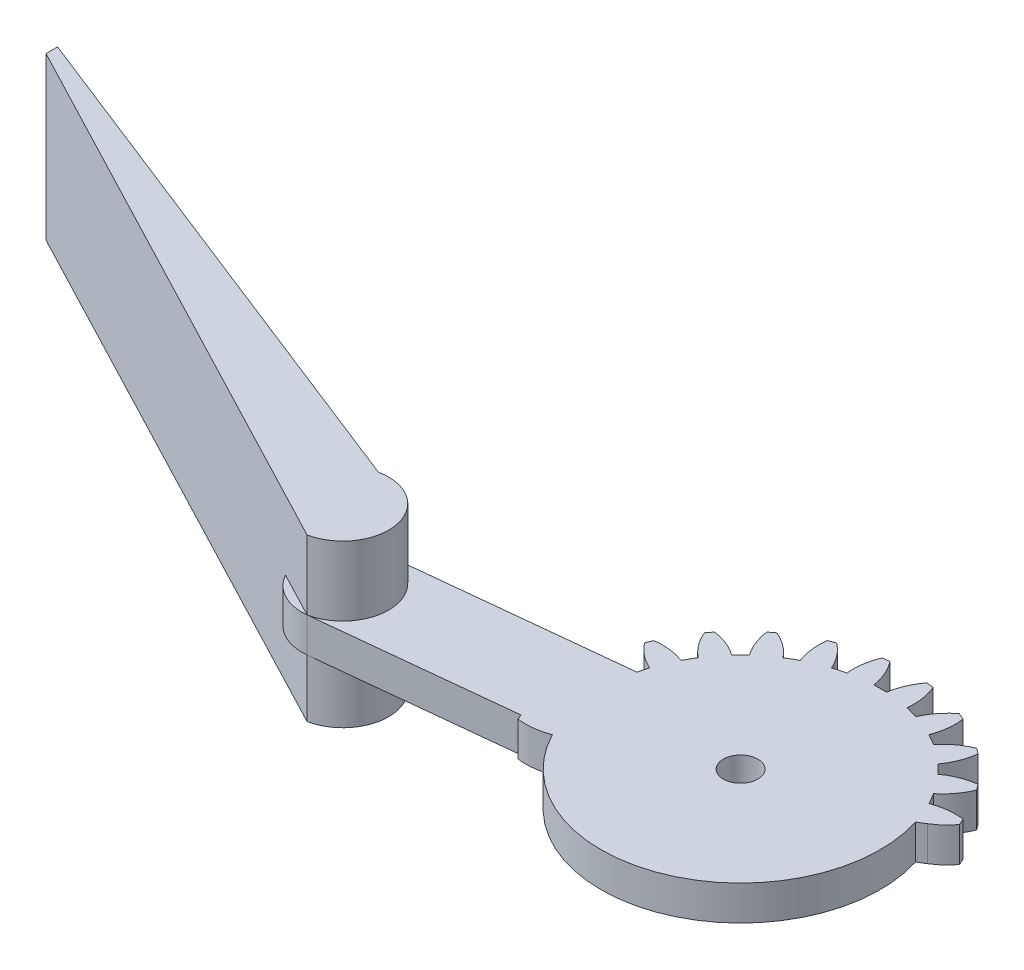
SolidWorks part; units mm, degrees
ref_plane "Front Plane" through (0, 0, 0) normal (0, 0, 1) x (1, 0, 0)
ref_plane "Top Plane" through (0, 0, 0) normal (0, 1, 0) x (1, 0, 0)
ref_plane "Right Plane" through (0, 0, 0) normal (1, 0, 0) x (0, 0, -1)
sketch "Sketch1" plane through (0, 0, 0) normal (0, 1, 0) x (1, 0, 0)
  line L0 (20.6437, 4) -> (2.0816, 4)
  line L1 (2.0816, -4) -> (20.6437, -4)
  arc A0 (2.0816, 4) -> (3.5217, 5.3071) centre (-0.7683, 8.5867) ccw
  arc A1 (3.5217, 5.3071) -> (3.2829, 5.8838) centre (-10.1063, 0) ccw
  arc A2 (3.2829, 5.8838) -> (0.6271, 5.5703) centre (2.5684, 0.5313) ccw
  arc A3 (0.6271, 5.5703) -> (0.0844, 6.5103) centre (-10.1063, 0) ccw
  arc A4 (0.0844, 6.5103) -> (1.6838, 8.6535) centre (-3.3089, 10.711) ccw
  arc A5 (1.6838, 8.6535) -> (1.3038, 9.1487) centre (-10.1063, 0) ccw
  arc A6 (1.3038, 9.1487) -> (-1.1803, 8.1585) centre (1.999, 3.7936) ccw
  arc A7 (-1.1803, 8.1585) -> (-1.9479, 8.926) centre (-10.1063, 0) ccw
  arc A8 (-1.9479, 8.926) -> (-0.9576, 11.4102) centre (-6.3127, 12.1053) ccw
  arc A9 (-0.9576, 11.4102) -> (-1.4528, 11.7901) centre (-10.1063, 0) ccw
  arc A10 (-1.4528, 11.7901) -> (-3.596, 10.1907) centre (0.6046, 6.7975) ccw
  arc A11 (-3.596, 10.1907) -> (-4.5361, 10.7334) centre (-10.1063, 0) ccw
  arc A12 (-4.5361, 10.7334) -> (-4.2225, 13.3892) centre (-9.5751, 12.6747) ccw
  arc A13 (-4.2225, 13.3892) -> (-4.7992, 13.6281) centre (-10.1063, 0) ccw
  arc A14 (-4.7992, 13.6281) -> (-6.4554, 11.5285) centre (-1.5196, 9.3381) ccw
  arc A15 (-6.4554, 11.5285) -> (-7.5039, 11.8094) centre (-10.1063, 0) ccw
  arc A16 (-7.5039, 11.8094) -> (-7.8884, 14.4558) centre (-12.8736, 12.3803) ccw
  arc A17 (-7.8884, 14.4558) -> (-8.5072, 14.5373) centre (-10.1063, 0) ccw
  arc A18 (-8.5072, 14.5373) -> (-9.5636, 12.0806) centre (-4.2291, 11.2423) ccw
  arc A19 (-9.5636, 12.0806) -> (-10.6491, 12.0806) centre (-10.1063, 0) ccw
  arc A20 (-10.6491, 12.0806) -> (-11.7054, 14.5373) centre (-15.9836, 11.2423) ccw
  arc A21 (-11.7054, 14.5373) -> (-12.3243, 14.4558) centre (-10.1063, 0) ccw
  arc A22 (-12.3243, 14.4558) -> (-12.7088, 11.8094) centre (-7.3391, 12.3803) ccw
  arc A23 (-12.7088, 11.8094) -> (-13.7573, 11.5285) centre (-10.1063, 0) ccw
  arc A24 (-13.7573, 11.5285) -> (-15.4135, 13.6281) centre (-18.6931, 9.3381) ccw
  arc A25 (-15.4135, 13.6281) -> (-15.9901, 13.3892) centre (-10.1063, 0) ccw
  arc A26 (-15.9901, 13.3892) -> (-15.6766, 10.7334) centre (-10.6376, 12.6747) ccw
  arc A27 (-15.6766, 10.7334) -> (-16.6166, 10.1907) centre (-10.1063, 0) ccw
  arc A28 (-16.6166, 10.1907) -> (-18.7599, 11.7901) centre (-20.8173, 6.7975) ccw
  arc A29 (-18.7599, 11.7901) -> (-19.255, 11.4102) centre (-10.1063, 0) ccw
  arc A30 (-19.255, 11.4102) -> (-18.2648, 8.926) centre (-13.9, 12.1053) ccw
  arc A31 (-18.2648, 8.926) -> (-19.0324, 8.1585) centre (-10.1063, 0) ccw
  arc A32 (-19.0324, 8.1585) -> (-21.5165, 9.1487) centre (-22.2117, 3.7936) ccw
  arc A33 (-21.5165, 9.1487) -> (-21.8965, 8.6535) centre (-10.1063, 0) ccw
  arc A34 (-21.8965, 8.6535) -> (-20.2971, 6.5103) centre (-16.9038, 10.711) ccw
  arc A35 (-20.2971, 6.5103) -> (-20.8398, 5.5703) centre (-10.1063, 0) ccw
  arc A36 (-20.8398, 5.5703) -> (-23.4956, 5.8838) centre (-22.7811, 0.5313) ccw
  arc A37 (-23.4956, 5.8838) -> (-23.7344, 5.3071) centre (-10.1063, 0) ccw
  arc A38 (-23.7344, 5.3071) -> (-21.6348, 3.6509) centre (-19.4444, 8.5867) ccw
  arc A39 (-21.6348, 3.6509) -> (-21.9157, 2.6025) centre (-10.1063, 0) ccw
  arc A40 (-21.9157, 2.6025) -> (-24.5622, 2.2179) centre (-22.4867, -2.7673) ccw
  arc A41 (-24.5622, 2.2179) -> (-24.6437, 1.5991) centre (-10.1063, 0) ccw
  arc A42 (-24.6437, 1.5991) -> (-22.1869, 0.5427) centre (-21.3486, 5.8773) ccw
  arc A43 (-22.1869, 0.5427) -> (-22.1869, -0.5427) centre (-10.1063, 0) ccw
  arc A44 (-22.1869, -0.5427) -> (-24.6437, -1.5991) centre (-21.3486, -5.8773) ccw
  arc A45 (-24.6437, -1.5991) -> (-24.5622, -2.2179) centre (-10.1063, 0) ccw
  arc A46 (-24.5622, -2.2179) -> (-21.9157, -2.6025) centre (-22.4867, 2.7673) ccw
  arc A47 (-21.9157, -2.6025) -> (-21.6348, -3.6509) centre (-10.1063, 0) ccw
  arc A48 (-21.6348, -3.6509) -> (-23.7344, -5.3071) centre (-19.4444, -8.5867) ccw
  arc A49 (-23.7344, -5.3071) -> (-23.4956, -5.8838) centre (-10.1063, 0) ccw
  arc A50 (-23.4956, -5.8838) -> (-20.8398, -5.5703) centre (-22.7811, -0.5313) ccw
  arc A51 (-20.8398, -5.5703) -> (-20.2971, -6.5103) centre (-10.1063, 0) ccw
  arc A52 (-20.2971, -6.5103) -> (-21.8965, -8.6535) centre (-16.9038, -10.711) ccw
  arc A53 (-21.8965, -8.6535) -> (-21.5165, -9.1487) centre (-10.1063, 0) ccw
  arc A54 (-21.5165, -9.1487) -> (-19.0324, -8.1585) centre (-22.2117, -3.7936) ccw
  arc A55 (-19.0324, -8.1585) -> (-18.2648, -8.926) centre (-10.1063, 0) ccw
  arc A56 (-18.2648, -8.926) -> (-19.255, -11.4102) centre (-13.9, -12.1053) ccw
  arc A57 (-19.255, -11.4102) -> (-18.7599, -11.7901) centre (-10.1063, 0) ccw
  arc A58 (-18.7599, -11.7901) -> (-16.6166, -10.1907) centre (-20.8173, -6.7975) ccw
  arc A59 (-16.6166, -10.1907) -> (-15.6766, -10.7334) centre (-10.1063, 0) ccw
  arc A60 (-15.6766, -10.7334) -> (-15.9901, -13.3892) centre (-10.6376, -12.6747) ccw
  arc A61 (-15.9901, -13.3892) -> (-15.4135, -13.6281) centre (-10.1063, 0) ccw
  arc A62 (-15.4135, -13.6281) -> (-13.7573, -11.5285) centre (-18.6931, -9.3381) ccw
  arc A63 (-13.7573, -11.5285) -> (-12.7088, -11.8094) centre (-10.1063, 0) ccw
  arc A64 (-12.7088, -11.8094) -> (-12.3243, -14.4558) centre (-7.3391, -12.3803) ccw
  arc A65 (-12.3243, -14.4558) -> (-11.7054, -14.5373) centre (-10.1063, 0) ccw
  arc A66 (-11.7054, -14.5373) -> (-10.6491, -12.0806) centre (-15.9836, -11.2423) ccw
  arc A67 (-10.6491, -12.0806) -> (-9.5636, -12.0806) centre (-10.1063, 0) ccw
  arc A68 (-9.5636, -12.0806) -> (-8.5072, -14.5373) centre (-4.2291, -11.2423) ccw
  arc A69 (-8.5072, -14.5373) -> (-7.8884, -14.4558) centre (-10.1063, 0) ccw
  arc A70 (-7.8884, -14.4558) -> (-7.5039, -11.8094) centre (-12.8736, -12.3803) ccw
  arc A71 (-7.5039, -11.8094) -> (-6.4554, -11.5285) centre (-10.1063, 0) ccw
  arc A72 (-6.4554, -11.5285) -> (-4.7992, -13.6281) centre (-1.5196, -9.3381) ccw
  arc A73 (-4.7992, -13.6281) -> (-4.2225, -13.3892) centre (-10.1063, 0) ccw
  arc A74 (-4.2225, -13.3892) -> (-4.5361, -10.7334) centre (-9.5751, -12.6747) ccw
  arc A75 (-4.5361, -10.7334) -> (-3.596, -10.1907) centre (-10.1063, 0) ccw
  arc A76 (-3.596, -10.1907) -> (-1.4528, -11.7901) centre (0.6046, -6.7975) ccw
  arc A77 (-1.4528, -11.7901) -> (-0.9576, -11.4102) centre (-10.1063, 0) ccw
  arc A78 (-0.9576, -11.4102) -> (-1.9479, -8.926) centre (-6.3127, -12.1053) ccw
  arc A79 (-1.9479, -8.926) -> (-1.1803, -8.1585) centre (-10.1063, 0) ccw
  arc A80 (-1.1803, -8.1585) -> (1.3038, -9.1487) centre (1.999, -3.7936) ccw
  arc A81 (1.3038, -9.1487) -> (1.6838, -8.6535) centre (-10.1063, 0) ccw
  arc A82 (1.6838, -8.6535) -> (0.0844, -6.5103) centre (-3.3089, -10.711) ccw
  arc A83 (0.0844, -6.5103) -> (0.6271, -5.5703) centre (-10.1063, 0) ccw
  arc A84 (0.6271, -5.5703) -> (3.2829, -5.8838) centre (2.5684, -0.5313) ccw
  arc A85 (3.2829, -5.8838) -> (3.5217, -5.3071) centre (-10.1063, 0) ccw
  arc A86 (3.5217, -5.3071) -> (2.0816, -4) centre (-0.7683, -8.5867) ccw
  arc A87 (20.6437, -4) -> (20.6437, 4) centre (20.6437, 0) ccw
  circle A88 centre (-10.1063, 0) radius 1.5
  circle A89 centre (20.6437, 0) radius 1.5
  dimension "D1" = 3
  dimension "D2" = 3
extrude "Boss-Extrude1" add sketch "Sketch1" along normal blind 3
sketch "Sketch3" plane through (0, 3, 0) normal (0, 1, 0) x (1, 0, 0)
  line L0 (-10.1063, 0) -> (-40.8563, 0) construction
  line L1 (-10.1063, 0) -> (-40.8563, -3.232)
  line L2 (-10.5245, 3.9781) -> (-41.2745, 0.7461)
  line L3 (-9.6882, -3.9781) -> (-40.4382, -7.21)
  circle A0 centre (-10.1063, 0) radius 1.5
  circle A1 centre (20.6437, 0) radius 1.5 construction
  circle A2 centre (20.6437, 0) radius 1.5
  circle A3 centre (-40.8563, -3.232) radius 1.5
  circle A4 centre (-40.8563, -3.232) radius 4
  circle A5 centre (-10.1063, 0) radius 4
  dimension "D2" = 3
  dimension "D5" = 3
  dimension "D6" = 8
  dimension "D7" = 8
  dimension "D1" = 30.75
  dimension "D3" = 30.75
  dimension "D4" = 6
extrude "Boss-Extrude2" add sketch "Sketch3" against normal blind 3 contours L0 A5 L2 | A5 L0 L2 A4 L1 | A4 A3 | A5 L1 A4 L3 | L0 A0 L1 A5 | A0 L0 A5 L1 region at (-13.0404, 3, 0.1538) region at (-12.8563, 3, -0.1131) region at (-28.6602, 3, 0.9475) region at (-23.811, 3, -1.3402) region at (-25.2642, 3, 3.6817) region at (-37.4885, 3, 1.2915)
sketch "Sketch4" plane through (0, 3, 0) normal (0, 1, 0) x (1, 0, 0)
  line L0 (20.6437, 4) -> (2.0816, 4) construction
  line L1 (2.0816, -4) -> (20.6437, -4) construction
  line L2 (20.6437, 4) -> (2.0816, 4)
  line L3 (2.0816, -4) -> (20.6437, -4)
  line L4 (2.0816, 4) -> (1.4381, 3.6001)
  line L5 (-23.2182, -5.4001) -> (-21.0377, -5.171)
  line L8 (-21.874, 2.7852) -> (-41.2745, 0.7461)
  line L9 (-40.4382, -7.21) -> (-23.6785, -5.4485)
  line L10 (2.0816, -4) -> (20.6437, -4)
  line L11 (20.6437, 4) -> (2.0816, 4)
  line L12 (-21.874, 2.7852) -> (-41.2745, 0.7461)
  line L13 (-40.4382, -7.21) -> (-23.6785, -5.4485)
  line L14 (2.0816, -4) -> (20.6437, -4)
  line L15 (20.6437, 4) -> (2.0816, 4)
  circle A0 centre (-10.1063, 0) radius 12.0927
  arc A1 (3.2829, 5.8838) -> (0.6271, 5.5703) centre (2.5684, 0.5313) ccw construction
  arc A2 (3.5217, 5.3071) -> (3.2829, 5.8838) centre (-10.1063, 0) ccw construction
  arc A3 (2.0816, 4) -> (3.5217, 5.3071) centre (-0.7683, 8.5867) ccw construction
  arc A4 (20.6437, -4) -> (20.6437, 4) centre (20.6437, 0) ccw construction
  arc A5 (3.5217, -5.3071) -> (2.0816, -4) centre (-0.7683, -8.5867) ccw construction
  arc A6 (3.2829, -5.8838) -> (3.5217, -5.3071) centre (-10.1063, 0) ccw construction
  arc A7 (0.6271, -5.5703) -> (3.2829, -5.8838) centre (2.5684, -0.5313) ccw construction
  arc A8 (3.2829, 5.8838) -> (0.6271, 5.5703) centre (2.5684, 0.5313) ccw
  arc A9 (3.5217, 5.3071) -> (3.2829, 5.8838) centre (-10.1063, 0) ccw
  arc A10 (2.0816, 4) -> (3.5217, 5.3071) centre (-0.7683, 8.5867) ccw
  arc A11 (20.6437, -4) -> (20.6437, 4) centre (20.6437, 0) ccw
  arc A12 (3.5217, -5.3071) -> (2.0816, -4) centre (-0.7683, -8.5867) ccw
  arc A13 (3.2829, -5.8838) -> (3.5217, -5.3071) centre (-10.1063, 0) ccw
  arc A14 (0.6271, -5.5703) -> (3.2829, -5.8838) centre (2.5684, -0.5313) ccw
  arc A95 (-23.6785, -5.4485) -> (-23.4956, -5.8838) centre (-10.1063, 0) ccw
  arc A96 (-41.2745, 0.7461) -> (-40.4382, -7.21) centre (-40.8563, -3.232) ccw
  arc A97 (-20.2971, -6.5103) -> (-21.8965, -8.6535) centre (-16.9038, -10.711) ccw
  arc A98 (-21.8965, -8.6535) -> (-21.5165, -9.1487) centre (-10.1063, 0) ccw
  arc A99 (-21.5165, -9.1487) -> (-19.0324, -8.1585) centre (-22.2117, -3.7936) ccw
  arc A100 (-19.0324, -8.1585) -> (-18.2648, -8.926) centre (-10.1063, 0) ccw
  arc A101 (-18.2648, -8.926) -> (-19.255, -11.4102) centre (-13.9, -12.1053) ccw
  arc A102 (-19.255, -11.4102) -> (-18.7599, -11.7901) centre (-10.1063, 0) ccw
  arc A103 (-18.7599, -11.7901) -> (-16.6166, -10.1907) centre (-20.8173, -6.7975) ccw
  arc A104 (-16.6166, -10.1907) -> (-15.6766, -10.7334) centre (-10.1063, 0) ccw
  arc A105 (-15.6766, -10.7334) -> (-15.9901, -13.3892) centre (-10.6376, -12.6747) ccw
  arc A106 (-15.9901, -13.3892) -> (-15.4135, -13.6281) centre (-10.1063, 0) ccw
  arc A107 (-15.4135, -13.6281) -> (-13.7573, -11.5285) centre (-18.6931, -9.3381) ccw
  arc A108 (-13.7573, -11.5285) -> (-12.7088, -11.8094) centre (-10.1063, 0) ccw
  arc A109 (-12.7088, -11.8094) -> (-12.3243, -14.4558) centre (-7.3391, -12.3803) ccw
  arc A110 (-12.3243, -14.4558) -> (-11.7054, -14.5373) centre (-10.1063, 0) ccw
  arc A111 (-11.7054, -14.5373) -> (-10.6491, -12.0806) centre (-15.9836, -11.2423) ccw
  arc A112 (-10.6491, -12.0806) -> (-9.5636, -12.0806) centre (-10.1063, 0) ccw
  arc A113 (-9.5636, -12.0806) -> (-8.5072, -14.5373) centre (-4.2291, -11.2423) ccw
  arc A114 (-8.5072, -14.5373) -> (-7.8884, -14.4558) centre (-10.1063, 0) ccw
  arc A115 (-7.8884, -14.4558) -> (-7.5039, -11.8094) centre (-12.8736, -12.3803) ccw
  arc A116 (-7.5039, -11.8094) -> (-6.4554, -11.5285) centre (-10.1063, 0) ccw
  arc A117 (-6.4554, -11.5285) -> (-4.7992, -13.6281) centre (-1.5196, -9.3381) ccw
  arc A118 (-4.7992, -13.6281) -> (-4.2225, -13.3892) centre (-10.1063, 0) ccw
  arc A119 (-4.2225, -13.3892) -> (-4.5361, -10.7334) centre (-9.5751, -12.6747) ccw
  arc A120 (-4.5361, -10.7334) -> (-3.596, -10.1907) centre (-10.1063, 0) ccw
  arc A121 (-3.596, -10.1907) -> (-1.4528, -11.7901) centre (0.6046, -6.7975) ccw
  arc A122 (-1.4528, -11.7901) -> (-0.9576, -11.4102) centre (-10.1063, 0) ccw
  arc A123 (-0.9576, -11.4102) -> (-1.9479, -8.926) centre (-6.3127, -12.1053) ccw
  arc A124 (-1.9479, -8.926) -> (-1.1803, -8.1585) centre (-10.1063, 0) ccw
  arc A125 (-1.1803, -8.1585) -> (1.3038, -9.1487) centre (1.999, -3.7936) ccw
  arc A126 (1.3038, -9.1487) -> (1.6838, -8.6535) centre (-10.1063, 0) ccw
  arc A127 (1.6838, -8.6535) -> (0.0844, -6.5103) centre (-3.3089, -10.711) ccw
  arc A128 (0.0844, -6.5103) -> (0.6271, -5.5703) centre (-10.1063, 0) ccw
  arc A129 (0.6271, -5.5703) -> (3.2829, -5.8838) centre (2.5684, -0.5313) ccw
  arc A130 (3.2829, -5.8838) -> (3.5217, -5.3071) centre (-10.1063, 0) ccw
  arc A131 (3.5217, -5.3071) -> (2.0816, -4) centre (-0.7683, -8.5867) ccw
  arc A132 (20.6437, -4) -> (20.6437, 4) centre (20.6437, 0) ccw
  arc A133 (2.0816, 4) -> (3.5217, 5.3071) centre (-0.7683, 8.5867) ccw
  arc A134 (3.5217, 5.3071) -> (3.2829, 5.8838) centre (-10.1063, 0) ccw
  arc A135 (3.2829, 5.8838) -> (0.6271, 5.5703) centre (2.5684, 0.5313) ccw
  arc A136 (0.6271, 5.5703) -> (0.0844, 6.5103) centre (-10.1063, 0) ccw
  arc A137 (0.0844, 6.5103) -> (1.6838, 8.6535) centre (-3.3089, 10.711) ccw
  arc A138 (1.6838, 8.6535) -> (1.3038, 9.1487) centre (-10.1063, 0) ccw
  arc A139 (1.3038, 9.1487) -> (-1.1803, 8.1585) centre (1.999, 3.7936) ccw
  arc A140 (-1.1803, 8.1585) -> (-1.9479, 8.926) centre (-10.1063, 0) ccw
  arc A141 (-1.9479, 8.926) -> (-0.9576, 11.4102) centre (-6.3127, 12.1053) ccw
  arc A142 (-0.9576, 11.4102) -> (-1.4528, 11.7901) centre (-10.1063, 0) ccw
  arc A143 (-1.4528, 11.7901) -> (-3.596, 10.1907) centre (0.6046, 6.7975) ccw
  arc A144 (-3.596, 10.1907) -> (-4.5361, 10.7334) centre (-10.1063, 0) ccw
  arc A145 (-4.5361, 10.7334) -> (-4.2225, 13.3892) centre (-9.5751, 12.6747) ccw
  arc A146 (-4.2225, 13.3892) -> (-4.7992, 13.6281) centre (-10.1063, 0) ccw
  arc A147 (-4.7992, 13.6281) -> (-6.4554, 11.5285) centre (-1.5196, 9.3381) ccw
  arc A148 (-6.4554, 11.5285) -> (-7.5039, 11.8094) centre (-10.1063, 0) ccw
  arc A149 (-7.5039, 11.8094) -> (-7.8884, 14.4558) centre (-12.8736, 12.3803) ccw
  arc A150 (-7.8884, 14.4558) -> (-8.5072, 14.5373) centre (-10.1063, 0) ccw
  arc A151 (-8.5072, 14.5373) -> (-9.5636, 12.0806) centre (-4.2291, 11.2423) ccw
  arc A152 (-9.5636, 12.0806) -> (-10.6491, 12.0806) centre (-10.1063, 0) ccw
  arc A153 (-10.6491, 12.0806) -> (-11.7054, 14.5373) centre (-15.9836, 11.2423) ccw
  arc A154 (-11.7054, 14.5373) -> (-12.3243, 14.4558) centre (-10.1063, 0) ccw
  arc A155 (-12.3243, 14.4558) -> (-12.7088, 11.8094) centre (-7.3391, 12.3803) ccw
  arc A156 (-12.7088, 11.8094) -> (-13.7573, 11.5285) centre (-10.1063, 0) ccw
  arc A157 (-13.7573, 11.5285) -> (-15.4135, 13.6281) centre (-18.6931, 9.3381) ccw
  arc A158 (-15.4135, 13.6281) -> (-15.9901, 13.3892) centre (-10.1063, 0) ccw
  arc A159 (-15.9901, 13.3892) -> (-15.6766, 10.7334) centre (-10.6376, 12.6747) ccw
  arc A160 (-15.6766, 10.7334) -> (-16.6166, 10.1907) centre (-10.1063, 0) ccw
  arc A161 (-16.6166, 10.1907) -> (-18.7599, 11.7901) centre (-20.8173, 6.7975) ccw
  arc A162 (-18.7599, 11.7901) -> (-19.255, 11.4102) centre (-10.1063, 0) ccw
  arc A163 (-19.255, 11.4102) -> (-18.2648, 8.926) centre (-13.9, 12.1053) ccw
  arc A164 (-18.2648, 8.926) -> (-19.0324, 8.1585) centre (-10.1063, 0) ccw
  arc A165 (-19.0324, 8.1585) -> (-21.5165, 9.1487) centre (-22.2117, 3.7936) ccw
  arc A166 (-21.5165, 9.1487) -> (-21.8965, 8.6535) centre (-10.1063, 0) ccw
  arc A167 (-21.8965, 8.6535) -> (-20.2971, 6.5103) centre (-16.9038, 10.711) ccw
  arc A168 (-20.2971, 6.5103) -> (-20.8398, 5.5703) centre (-10.1063, 0) ccw
  arc A169 (-20.8398, 5.5703) -> (-23.4956, 5.8838) centre (-22.7811, 0.5313) ccw
  arc A170 (-23.4956, 5.8838) -> (-23.7344, 5.3071) centre (-10.1063, 0) ccw
  arc A171 (-23.7344, 5.3071) -> (-21.6348, 3.6509) centre (-19.4444, 8.5867) ccw
  arc A172 (-21.6348, 3.6509) -> (-21.874, 2.7852) centre (-10.1063, 0) ccw
  arc A173 (-23.6785, -5.4485) -> (-23.4956, -5.8838) centre (-10.1063, 0) ccw
  arc A174 (-23.4956, -5.8838) -> (-20.8398, -5.5703) centre (-22.7811, -0.5313) ccw
  arc A175 (-23.4956, -5.8838) -> (-20.8398, -5.5703) centre (-22.7811, -0.5313) ccw
  arc A176 (-41.2745, 0.7461) -> (-40.4382, -7.21) centre (-40.8563, -3.232) ccw
  arc A177 (-20.2971, -6.5103) -> (-21.8965, -8.6535) centre (-16.9038, -10.711) ccw
  arc A178 (-21.8965, -8.6535) -> (-21.5165, -9.1487) centre (-10.1063, 0) ccw
  arc A179 (-21.5165, -9.1487) -> (-19.0324, -8.1585) centre (-22.2117, -3.7936) ccw
  arc A180 (-19.0324, -8.1585) -> (-18.2648, -8.926) centre (-10.1063, 0) ccw
  arc A181 (-18.2648, -8.926) -> (-19.255, -11.4102) centre (-13.9, -12.1053) ccw
  arc A182 (-19.255, -11.4102) -> (-18.7599, -11.7901) centre (-10.1063, 0) ccw
  arc A183 (-18.7599, -11.7901) -> (-16.6166, -10.1907) centre (-20.8173, -6.7975) ccw
  arc A184 (-16.6166, -10.1907) -> (-15.6766, -10.7334) centre (-10.1063, 0) ccw
  arc A185 (-15.6766, -10.7334) -> (-15.9901, -13.3892) centre (-10.6376, -12.6747) ccw
  arc A186 (-15.9901, -13.3892) -> (-15.4135, -13.6281) centre (-10.1063, 0) ccw
  arc A187 (-15.4135, -13.6281) -> (-13.7573, -11.5285) centre (-18.6931, -9.3381) ccw
  arc A188 (-13.7573, -11.5285) -> (-12.7088, -11.8094) centre (-10.1063, 0) ccw
  arc A189 (-12.7088, -11.8094) -> (-12.3243, -14.4558) centre (-7.3391, -12.3803) ccw
  arc A190 (-12.3243, -14.4558) -> (-11.7054, -14.5373) centre (-10.1063, 0) ccw
  arc A191 (-11.7054, -14.5373) -> (-10.6491, -12.0806) centre (-15.9836, -11.2423) ccw
  arc A192 (-10.6491, -12.0806) -> (-9.5636, -12.0806) centre (-10.1063, 0) ccw
  arc A193 (-9.5636, -12.0806) -> (-8.5072, -14.5373) centre (-4.2291, -11.2423) ccw
  arc A194 (-8.5072, -14.5373) -> (-7.8884, -14.4558) centre (-10.1063, 0) ccw
  arc A195 (-7.8884, -14.4558) -> (-7.5039, -11.8094) centre (-12.8736, -12.3803) ccw
  arc A196 (-7.5039, -11.8094) -> (-6.4554, -11.5285) centre (-10.1063, 0) ccw
  arc A197 (-6.4554, -11.5285) -> (-4.7992, -13.6281) centre (-1.5196, -9.3381) ccw
  arc A198 (-4.7992, -13.6281) -> (-4.2225, -13.3892) centre (-10.1063, 0) ccw
  arc A199 (-4.2225, -13.3892) -> (-4.5361, -10.7334) centre (-9.5751, -12.6747) ccw
  arc A200 (-4.5361, -10.7334) -> (-3.596, -10.1907) centre (-10.1063, 0) ccw
  arc A201 (-3.596, -10.1907) -> (-1.4528, -11.7901) centre (0.6046, -6.7975) ccw
  arc A202 (-1.4528, -11.7901) -> (-0.9576, -11.4102) centre (-10.1063, 0) ccw
  arc A203 (-0.9576, -11.4102) -> (-1.9479, -8.926) centre (-6.3127, -12.1053) ccw
  arc A204 (-1.9479, -8.926) -> (-1.1803, -8.1585) centre (-10.1063, 0) ccw
  arc A205 (-1.1803, -8.1585) -> (1.3038, -9.1487) centre (1.999, -3.7936) ccw
  arc A206 (1.3038, -9.1487) -> (1.6838, -8.6535) centre (-10.1063, 0) ccw
  arc A207 (1.6838, -8.6535) -> (0.0844, -6.5103) centre (-3.3089, -10.711) ccw
  arc A208 (0.0844, -6.5103) -> (0.6271, -5.5703) centre (-10.1063, 0) ccw
  arc A209 (0.6271, -5.5703) -> (3.2829, -5.8838) centre (2.5684, -0.5313) ccw
  arc A210 (3.2829, -5.8838) -> (3.5217, -5.3071) centre (-10.1063, 0) ccw
  arc A211 (3.5217, -5.3071) -> (2.0816, -4) centre (-0.7683, -8.5867) ccw
  arc A212 (20.6437, -4) -> (20.6437, 4) centre (20.6437, 0) ccw
  arc A213 (2.0816, 4) -> (3.5217, 5.3071) centre (-0.7683, 8.5867) ccw
  arc A214 (3.5217, 5.3071) -> (3.2829, 5.8838) centre (-10.1063, 0) ccw
  arc A215 (3.2829, 5.8838) -> (0.6271, 5.5703) centre (2.5684, 0.5313) ccw
  arc A216 (0.6271, 5.5703) -> (0.0844, 6.5103) centre (-10.1063, 0) ccw
  arc A217 (0.0844, 6.5103) -> (1.6838, 8.6535) centre (-3.3089, 10.711) ccw
  arc A218 (1.6838, 8.6535) -> (1.3038, 9.1487) centre (-10.1063, 0) ccw
  arc A219 (1.3038, 9.1487) -> (-1.1803, 8.1585) centre (1.999, 3.7936) ccw
  arc A220 (-1.1803, 8.1585) -> (-1.9479, 8.926) centre (-10.1063, 0) ccw
  arc A221 (-1.9479, 8.926) -> (-0.9576, 11.4102) centre (-6.3127, 12.1053) ccw
  arc A222 (-0.9576, 11.4102) -> (-1.4528, 11.7901) centre (-10.1063, 0) ccw
  arc A223 (-1.4528, 11.7901) -> (-3.596, 10.1907) centre (0.6046, 6.7975) ccw
  arc A224 (-3.596, 10.1907) -> (-4.5361, 10.7334) centre (-10.1063, 0) ccw
  arc A225 (-4.5361, 10.7334) -> (-4.2225, 13.3892) centre (-9.5751, 12.6747) ccw
  arc A226 (-4.2225, 13.3892) -> (-4.7992, 13.6281) centre (-10.1063, 0) ccw
  arc A227 (-4.7992, 13.6281) -> (-6.4554, 11.5285) centre (-1.5196, 9.3381) ccw
  arc A228 (-6.4554, 11.5285) -> (-7.5039, 11.8094) centre (-10.1063, 0) ccw
  arc A229 (-7.5039, 11.8094) -> (-7.8884, 14.4558) centre (-12.8736, 12.3803) ccw
  arc A230 (-7.8884, 14.4558) -> (-8.5072, 14.5373) centre (-10.1063, 0) ccw
  arc A231 (-8.5072, 14.5373) -> (-9.5636, 12.0806) centre (-4.2291, 11.2423) ccw
  arc A232 (-9.5636, 12.0806) -> (-10.6491, 12.0806) centre (-10.1063, 0) ccw
  arc A233 (-10.6491, 12.0806) -> (-11.7054, 14.5373) centre (-15.9836, 11.2423) ccw
  arc A234 (-11.7054, 14.5373) -> (-12.3243, 14.4558) centre (-10.1063, 0) ccw
  arc A235 (-12.3243, 14.4558) -> (-12.7088, 11.8094) centre (-7.3391, 12.3803) ccw
  arc A236 (-12.7088, 11.8094) -> (-13.7573, 11.5285) centre (-10.1063, 0) ccw
  arc A237 (-13.7573, 11.5285) -> (-15.4135, 13.6281) centre (-18.6931, 9.3381) ccw
  arc A238 (-15.4135, 13.6281) -> (-15.9901, 13.3892) centre (-10.1063, 0) ccw
  arc A239 (-15.9901, 13.3892) -> (-15.6766, 10.7334) centre (-10.6376, 12.6747) ccw
  arc A240 (-15.6766, 10.7334) -> (-16.6166, 10.1907) centre (-10.1063, 0) ccw
  arc A241 (-16.6166, 10.1907) -> (-18.7599, 11.7901) centre (-20.8173, 6.7975) ccw
  arc A242 (-18.7599, 11.7901) -> (-19.255, 11.4102) centre (-10.1063, 0) ccw
  arc A243 (-19.255, 11.4102) -> (-18.2648, 8.926) centre (-13.9, 12.1053) ccw
  arc A244 (-18.2648, 8.926) -> (-19.0324, 8.1585) centre (-10.1063, 0) ccw
  arc A245 (-19.0324, 8.1585) -> (-21.5165, 9.1487) centre (-22.2117, 3.7936) ccw
  arc A246 (-21.5165, 9.1487) -> (-21.8965, 8.6535) centre (-10.1063, 0) ccw
  arc A247 (-21.8965, 8.6535) -> (-20.2971, 6.5103) centre (-16.9038, 10.711) ccw
  arc A248 (-20.2971, 6.5103) -> (-20.8398, 5.5703) centre (-10.1063, 0) ccw
  arc A249 (-20.8398, 5.5703) -> (-23.4956, 5.8838) centre (-22.7811, 0.5313) ccw
  arc A250 (-23.4956, 5.8838) -> (-23.7344, 5.3071) centre (-10.1063, 0) ccw
  arc A251 (-23.7344, 5.3071) -> (-21.6348, 3.6509) centre (-19.4444, 8.5867) ccw
  arc A252 (-21.6348, 3.6509) -> (-21.874, 2.7852) centre (-10.1063, 0) ccw
  arc A253 (-20.8398, -5.5703) -> (-20.2971, -6.5103) centre (-10.1063, 0) ccw
  arc A254 (-20.8398, -5.5703) -> (-20.2971, -6.5103) centre (-10.1063, 0) ccw
  dimension "D2" = 24.1855
  dimension "D1" = 0
extrude "Cut-Extrude1" cut sketch "Sketch4" against normal blind 3 contours A178 A179 A0 L5 A177 | A182 A183 A0 A181 | A186 A187 A0 A185 | A190 A191 A0 A189 | A194 A195 A0 A193 | A198 A199 A0 A197 | A202 A203 A0 A201 | A206 A207 A0 A205 | A0 A14 A13 A12 L3 A11 L2 L4 region at (12.5694, 3, 0.1127) region at (0.3325, 3, 8.01) region at (-2.0963, 3, 10.4389) region at (-5.071, 3, 12.1563) region at (-8.3889, 3, 13.0454) region at (-11.8238, 3, 13.0454) region at (-15.1417, 3, 12.1563) region at (-18.1164, 3, 10.4389) region at (-20.5452, 3, 8.01)
sketch "Sketch5" plane through (0, 3, 0) normal (0, 1, 0) x (1, 0, 0)
  line L0 (-42.0536, 0.5847) -> (-87.8493, 18.5908)
  line L1 (-40.4382, -7.21) -> (-87.8493, 17.5895)
  line L2 (-87.8493, 17.5895) -> (-87.8493, 18.5908)
  arc A0 (-41.2745, 0.7461) -> (-40.4382, -7.21) centre (-40.8563, -3.232) ccw construction
  arc A1 (-42.0536, 0.5847) -> (-40.4382, -7.21) centre (-41.2459, -3.3127) cw
extrude "Boss-Extrude3" add sketch "Sketch5" along normal blind 6 and the other way blind 8
